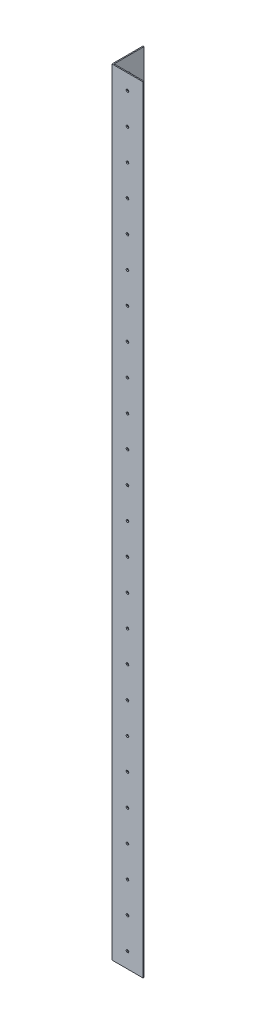
SolidWorks part; units mm, degrees
ref_plane "Спереди" through (0, 0, 0) normal (0, 0, 1) x (1, 0, 0)
ref_plane "Сверху" through (0, 0, 0) normal (0, 1, 0) x (1, 0, 0)
ref_plane "Справа" through (0, 0, 0) normal (1, 0, 0) x (0, 0, -1)
sketch "Эскиз1" plane through (0, 0, 0) normal (0, 1, 0) x (1, 0, 0)
  line L0 (0, 60) -> (0, 0)
  line L1 (0, 0) -> (60, 0)
extrude "Вытянуть-Тонкостенный1" add sketch "Эскиз1" along normal blind 1500 thin thin type one direction reverse wall 2
sketch "Эскиз2" plane through (0, 0, 0) normal (-1, 0, 0) x (0, 0, 1)
  circle A0 centre (-30, 30) radius 2.5
  circle A1 centre (-30, 90) radius 2.5
  circle A2 centre (-30, 150) radius 2.5
  circle A3 centre (-30, 210) radius 2.5
  circle A4 centre (-30, 270) radius 2.5
  circle A5 centre (-30, 330) radius 2.5
  circle A6 centre (-30, 390) radius 2.5
  circle A7 centre (-30, 450) radius 2.5
  circle A8 centre (-30, 510) radius 2.5
  circle A9 centre (-30, 570) radius 2.5
  circle A10 centre (-30, 630) radius 2.5
  circle A11 centre (-30, 690) radius 2.5
  circle A12 centre (-30, 750) radius 2.5
  circle A13 centre (-30, 810) radius 2.5
  circle A14 centre (-30, 870) radius 2.5
  circle A15 centre (-30, 930) radius 2.5
  circle A16 centre (-30, 990) radius 2.5
  circle A17 centre (-30, 1050) radius 2.5
  circle A18 centre (-30, 1110) radius 2.5
  circle A19 centre (-30, 1170) radius 2.5
  circle A20 centre (-30, 1230) radius 2.5
  circle A21 centre (-30, 1290) radius 2.5
  circle A22 centre (-30, 1350) radius 2.5
  circle A23 centre (-30, 1410) radius 2.5
  circle A24 centre (-30, 1470) radius 2.5
  dimension "D1" = 25
extrude "Вырез-Вытянуть1" cut sketch "Эскиз2" against normal through all
sketch "Эскиз3" plane through (0, 0, 0) normal (0, 0, 1) x (1, 0, 0)
  circle A0 centre (30, 30) radius 2.5
  circle A1 centre (30, 90) radius 2.5
  circle A2 centre (30, 150) radius 2.5
  circle A3 centre (30, 210) radius 2.5
  circle A4 centre (30, 270) radius 2.5
  circle A5 centre (30, 330) radius 2.5
  circle A6 centre (30, 390) radius 2.5
  circle A7 centre (30, 450) radius 2.5
  circle A8 centre (30, 510) radius 2.5
  circle A9 centre (30, 570) radius 2.5
  circle A10 centre (30, 630) radius 2.5
  circle A11 centre (30, 690) radius 2.5
  circle A12 centre (30, 750) radius 2.5
  circle A13 centre (30, 810) radius 2.5
  circle A14 centre (30, 870) radius 2.5
  circle A15 centre (30, 930) radius 2.5
  circle A16 centre (30, 990) radius 2.5
  circle A17 centre (30, 1050) radius 2.5
  circle A18 centre (30, 1110) radius 2.5
  circle A19 centre (30, 1170) radius 2.5
  circle A20 centre (30, 1230) radius 2.5
  circle A21 centre (30, 1290) radius 2.5
  circle A22 centre (30, 1350) radius 2.5
  circle A23 centre (30, 1410) radius 2.5
  circle A24 centre (30, 1470) radius 2.5
  dimension "D1" = 25
extrude "Вырез-Вытянуть2" cut sketch "Эскиз3" against normal through all
